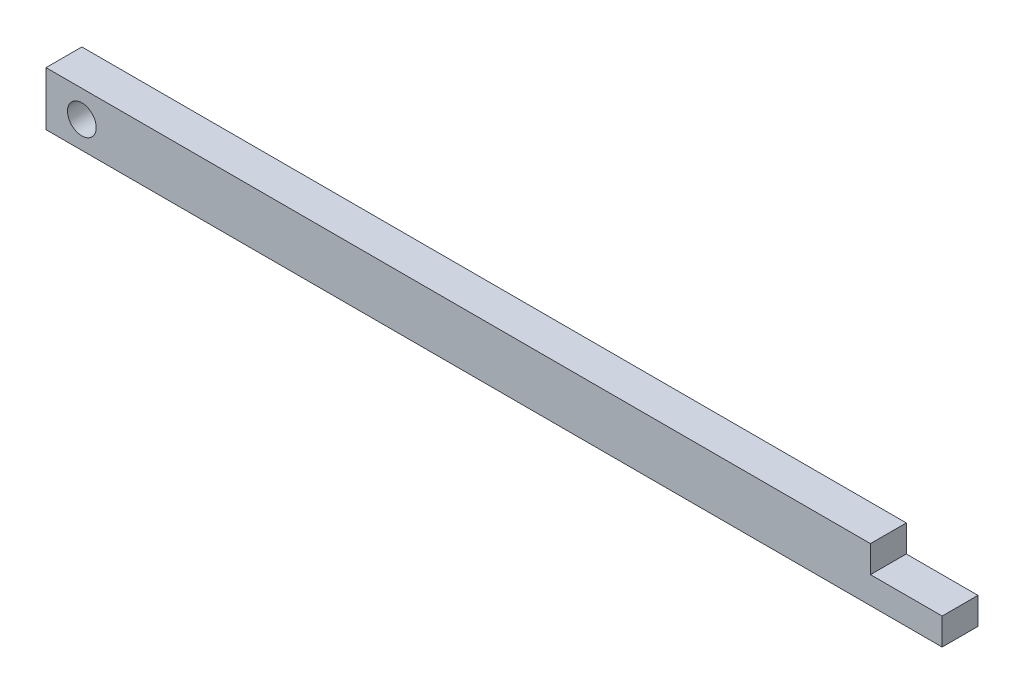
SolidWorks part; units mm, degrees
ref_plane "Front Plane" through (0, 0, 0) normal (0, 0, 1) x (1, 0, 0)
ref_plane "Top Plane" through (0, 0, 0) normal (0, 1, 0) x (1, 0, 0)
ref_plane "Right Plane" through (0, 0, 0) normal (1, 0, 0) x (0, 0, -1)
sketch "Sketch1" plane through (0, 0, 0) normal (0, 0, 1) x (1, 0, 0)
  line L0 (250, 7.5) -> (230, 7.5)
  line L1 (0, 0) -> (250, 0)
  line L2 (0, 0) -> (0, 15)
  line L3 (0, 15) -> (230, 15)
  line L4 (250, 0) -> (250, 7.5)
  line L5 (230, 7.5) -> (230, 15)
  circle A0 centre (10, 7.5) radius 3.1785
  point P9 (0, 7.5)
  dimension "D1" = 15
  dimension "D2" = 250
  dimension "D3" = 10
  dimension "D4" = 7.5
  dimension "D5" = 7.5
  dimension "D6" = 20
extrude "Boss-Extrude1" add sketch "Sketch1" along normal blind 10 contours L3 L5 L0 L4 L1 L2
sketch "Sketch3" plane through (0, 0, 10) normal (0, 0, 1) x (1, 0, 0)
  line L0 (0, 0) -> (250, 0) construction
  line L1 (0, 0) -> (0, 15) construction
  circle A0 centre (10, 7.5) radius 4
  dimension "D1" = 8
  dimension "D2" = 10
  dimension "7.5" = 7.5
extrude "Cut-Extrude1" cut sketch "Sketch3" against normal blind 10
